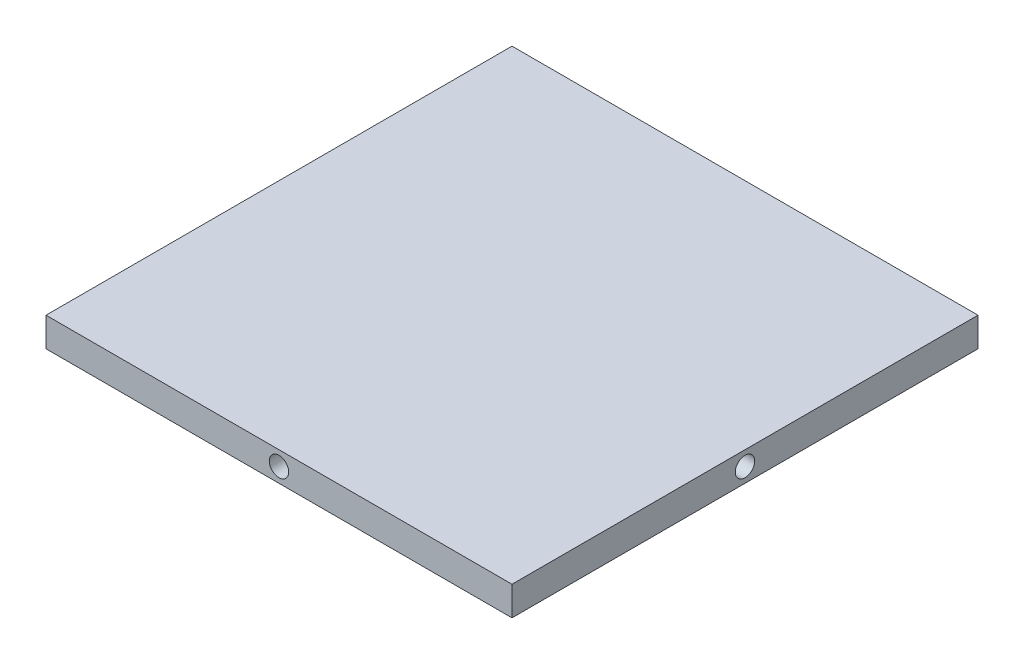
SolidWorks part; units mm, degrees
ref_plane "Front Plane" through (0, 0, 0) normal (0, 0, 1) x (1, 0, 0)
ref_plane "Top Plane" through (0, 0, 0) normal (0, 1, 0) x (1, 0, 0)
ref_plane "Right Plane" through (0, 0, 0) normal (1, 0, 0) x (0, 0, -1)
sketch "Sketch1" plane through (0, 0, 0) normal (0, 1, 0) x (1, 0, 0)
  line L1 (-76.2, -76.2) -> (76.2, -76.2)
  line L2 (-76.2, -76.2) -> (-76.2, 76.2)
  line L3 (-76.2, 76.2) -> (76.2, 76.2)
  line L4 (76.2, -76.2) -> (76.2, 76.2)
  line L5 (-76.2, -76.2) -> (76.2, 76.2) construction
  line L6 (-76.2, 76.2) -> (76.2, -76.2) construction
  point P0 (0, 0)
  dimension "D1" = 152.4
  dimension "D2" = 152.4
extrude "Boss-Extrude1" add sketch "Sketch1" along normal mid plane 9.525
hole_wizard "1/4 (0.25) Diameter Hole1" positions "Sketch2" profile "Sketch3" hole size "1/4" standard "ANSI Inch"
sketch "Sketch2" plane through (76.2, 0, 0) normal (1, 0, 0) x (0, 0, -1)
  point P0 (0, 0)
sketch "Sketch3" plane through (76.2, 0, 0) normal (0, 1, 0) x (0, 0, -1)
  line L0 (0, 0) -> (0, 14.6077)
  line L1 (0, 14.6077) -> (3.175, 12.7)
  line L2 (3.175, 12.7) -> (3.175, 0)
  line L5 (3.175, 0) -> (0, 0)
  line L10 (0, 14.6077) -> (-3.175, 12.7) construction
  line L11 (0, -6.35) -> (0, 107.95) construction
  dimension "Hole Dia." = 6.35
  dimension "Hole Depth" = 12.7
  dimension "Drill Angle" = 118
pattern_circular "CirPattern1" count 4 over 360 about axis through (0, 4.7625, 0) along (0, 1, 0) of "1/4 (0.25) Diameter Hole1"
sketch "Sketch4" plane through (0, 4.7625, 0) normal (0, 1, 0) x (1, 0, 0)
  line L0 (-76.2, -76.2) -> (76.2, 76.2)
ref_axis "Axis1" through (76.2, 4.7625, 76.2) along (-0.7071, 0, -0.7071)
ref_point "Point1"
ref_point "Point2"
ref_point "Point3"
ref_point "Point4"
